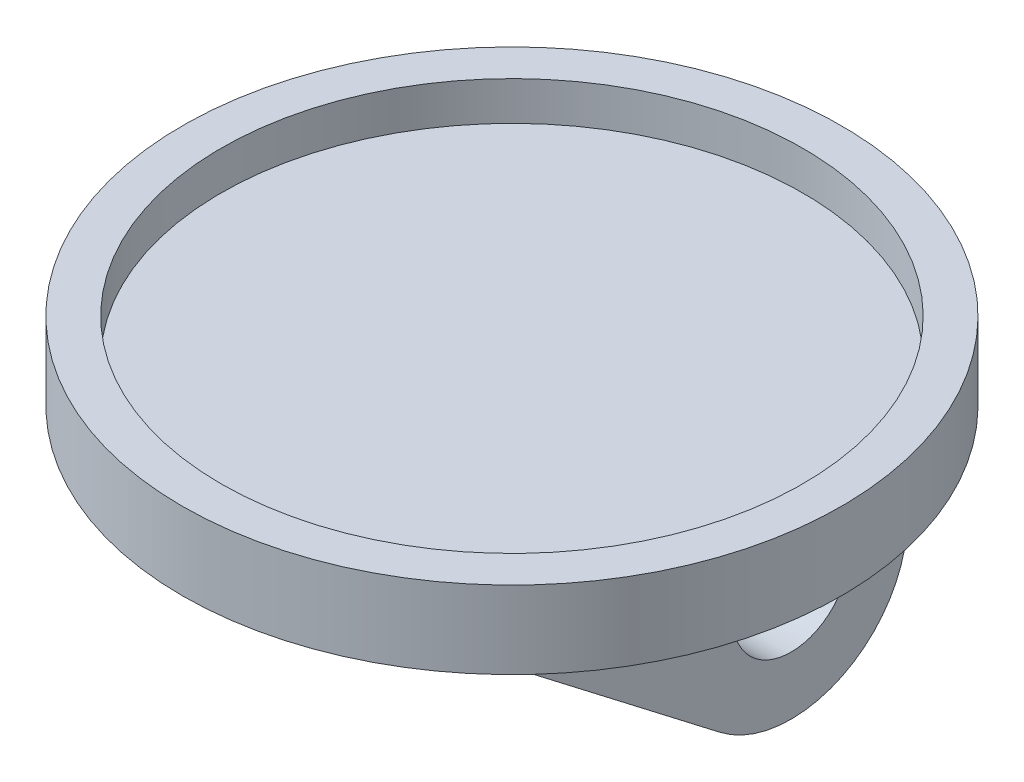
SolidWorks part; units mm, degrees
ref_plane "Front Plane" through (0, 0, 0) normal (0, 0, 1) x (1, 0, 0)
ref_plane "Top Plane" through (0, 0, 0) normal (0, 1, 0) x (1, 0, 0)
ref_plane "Right Plane" through (0, 0, 0) normal (1, 0, 0) x (0, 0, -1)
sketch "Connector Plate Sketch" plane through (0, 0, 0) normal (0, 1, 0) x (1, 0, 0)
  circle A1 centre (0, 0) radius 85
  dimension "D2" = 170
extrude "Connector Plate Extrude" add sketch "Connector Plate Sketch" along normal blind 20
shell "Connector Plate Shell" thickness 10 removed face at (0, 20, 85)
sketch "Triangle Sketch" plane through (0, 0, 0) normal (1, 0, 0) x (0, 0, -1)
  line L0 (65, -100) -> (-65, 0)
  line L1 (-65, 0) -> (65, 0)
  line L2 (65, 0) -> (65, -100)
  line L3 (-85, 0) -> (85, 0) construction
  line L4 (35, -39.0741) -> (16.7087, -62.8528) construction
  line L5 (35, -39.0741) -> (65, -39.0741) construction
  circle A0 centre (35, -39.0741) radius 15
  point P10 (0, 0)
  dimension "D1" = 30
  dimension "D3" = 30
  dimension "D5" = 100
  dimension "D6" = 130
extrude "Triangle Extrude 1" add sketch "Triangle Sketch" along normal blind 20 from offset 17
extrude "Triangle Extrude 2" add sketch "Triangle Sketch<3>" against normal blind 20 from offset 17 offset against normal yes
sketch "Triangle Sketch<3>" plane through (0, 0, 0) normal (1, 0, 0) x (0, 0, -1) same geometry as "Triangle Sketch"
fillet "Triangle Fillet" radius 30 2 edges at (27, -100, -65) (-27, -100, -65)
